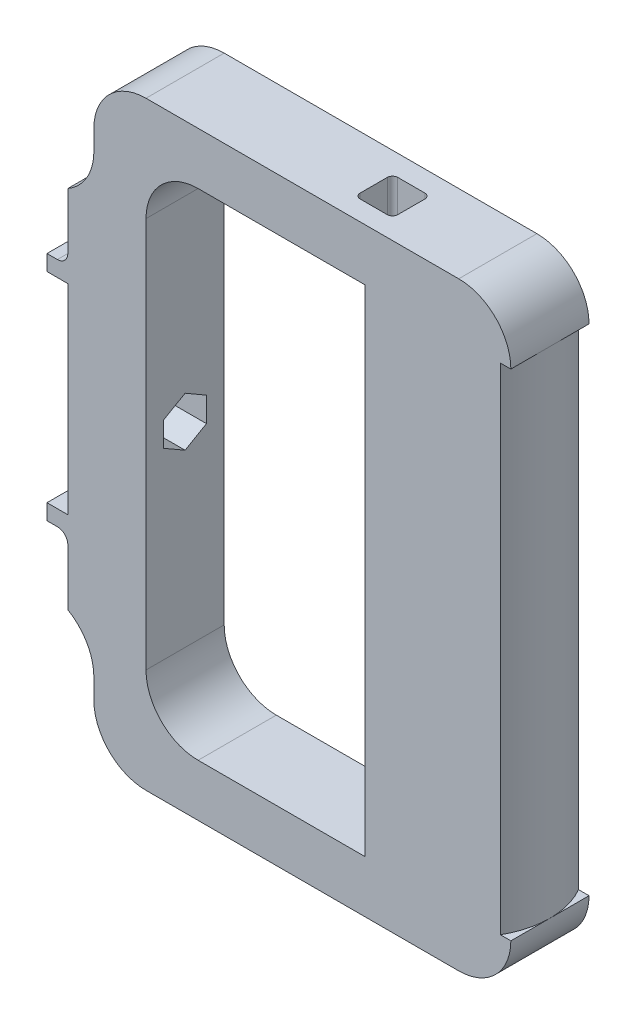
SolidWorks part; units mm, degrees
material "ABS"
ref_plane "Front Plane" through (0, 0, 0) normal (0, 0, 1) x (1, 0, 0)
ref_plane "Top Plane" through (0, 0, 0) normal (0, 1, 0) x (1, 0, 0)
ref_plane "Right Plane" through (0, 0, 0) normal (1, 0, 0) x (0, 0, -1)
sketch "Model" plane through (0, 0, 0) normal (0, 0, 1) x (1, 0, 0)
  line L0 (80, 115) -> (80, 105)
  line L1 (80, 0) -> (80, 10)
  line L8 (-5, 92.5) -> (0, 92.5)
  line L9 (-5, 22.5) -> (0, 22.5)
  line L10 (-5, 92.5) -> (-5, 22.5)
  line L11 (0, 115) -> (80, 115)
  line L12 (0, 0) -> (80, 0)
  line L13 (80, 105) -> (10, 105)
  line L14 (80, 10) -> (10, 10)
  line L16 (10, 105) -> (10, 10)
  line L17 (0, 115) -> (0, 92.5)
  line L19 (0, 0) -> (0, 22.5)
  dimension "D1" = 10
  dimension "D2" = 10
  dimension "D3" = 5
  dimension "D4" = 10
  dimension "D5" = 10
  dimension "D6" = 70
  dimension "D7" = 70
  dimension "D8" = 22.5
  dimension "D9" = 70
  dimension "D10" = 22.5
extrude "Main Body" add sketch "Model" along normal blind 15
sketch "Sketch2" plane through (-5, 0, 0) normal (-1, 0, 0) x (0, 0, 1)
  line L0 (15, 92.5) -> (0, 92.5) construction
  line L2 (7.5, 92.5) -> (7.5, 22.5) construction
  line L3 (15, 22.5) -> (0, 22.5) construction
  circle A0 centre (7.5, 57.5) radius 2.725
  dimension "D3" = 5.45
extrude "M5 Hole" cut sketch "Sketch2" against normal up to next
sketch "Sketch6" plane through (0, 105, 0) normal (0, -1, 0) x (1, 0, 0)
  line L1 (52.0096, 15) -> (77.9904, 15)
  line L2 (52.0096, 0) -> (77.9904, 0)
  line L3 (10, 15) -> (80, 15) construction
  line L4 (10, 0) -> (80, 0) construction
  line L5 (10, 15) -> (10, 0) construction
  line L6 (80, 15) -> (80, 0) construction
  arc A0 (52.0096, 15) -> (52.0096, 0) centre (65, 7.5) ccw
  arc A1 (77.9904, 15) -> (77.9904, 0) centre (65, 7.5) cw
  dimension "D3" = 15
  dimension "D4" = 15
  dimension "D5" = 15
  dimension "D2" = 7.5
extrude "Grip" add sketch "Sketch6" along normal up to next
sketch "Sketch8" plane through (0, 115, 0) normal (0, 1, 0) x (1, 0, 0)
  line L0 (80, -15) -> (80, 0) construction
  line L2 (80, 0) -> (0, 0) construction
  line L3 (46.3, -4) -> (53.5, -4)
  line L4 (46.3, -4) -> (46.3, -11.2)
  line L5 (46.3, -11.2) -> (53.5, -11.2)
  line L6 (53.5, -4) -> (53.5, -11.2)
  line L7 (46.3, -4) -> (53.5, -11.2) construction
  line L8 (46.3, -11.2) -> (53.5, -4) construction
  dimension "D2" = 7.2
  dimension "D3" = 26.5
  dimension "D4" = 4
extrude "Button 1" cut sketch "Sketch8" against normal blind 7
sketch "Sketch9" plane through (0, 108, 0) normal (0, 1, 0) x (1, 0, 0)
  line L4 (46.3, -4) -> (46.3, -11.2) construction
  line L5 (46.3, -11.2) -> (53.5, -11.2) construction
  circle A0 centre (49.7986, -7.7) radius 2
  point P3 (46.3, -7.6)
  dimension "D1" = 4
  dimension "D2" = 3.5
  dimension "D3" = 3.5
extrude "Hole Wires Button 1" cut sketch "Sketch9" against normal blind 3
fillet "Outer Fillet" radius 10 8 edges at (80, 115, 7.5) (80, 0, 7.5) (0, 0, 7.5) (0, 22.5, 7.5) (10, 10, 7.5) (10, 105, 7.5) (0, 92.5, 7.5) (0, 115, 7.5)
sketch "Sketch13" plane through (0, 0, 0) normal (0, 0, -1) x (-1, 0, 0)
  line L0 (-70, 115) -> (-10, 115) construction
  line L2 (-13.7, 112) -> (-6.5, 112)
  line L3 (-13.7, 112) -> (-13.7, 104.8)
  line L4 (-13.7, 104.8) -> (-6.5, 104.8)
  line L5 (-6.5, 112) -> (-6.5, 104.8)
  line L6 (-13.7, 112) -> (-6.5, 104.8) construction
  line L7 (-13.7, 104.8) -> (-6.5, 112) construction
  line L8 (0, 105) -> (0, 101.1603) construction
  point P3 (-10.1, 108.4)
  dimension "D2" = 7.2
  dimension "D3" = 3
  dimension "D4" = 6.5
extrude "Button 2" cut sketch "Sketch13" against normal blind 10
fillet "Buttons Fillet" radius 1 8 edges at (53.5, 111.5, 4) (53.5, 111.5, 11.2) (46.3, 111.5, 4) (46.3, 111.5, 11.2) (6.5, 104.8, 5) (13.7, 104.8, 5) (13.7, 112, 5) (6.5, 112, 5)
ref_plane "Wire Routing Plane" through (10, 0, 0) normal (1, 0, 0) x (0, 0, -1)
sketch "Sketch16" plane through (10, 0, 0) normal (1, 0, 0) x (0, 0, -1)
  line L0 (0, 95) -> (-15, 95) construction
  circle A0 centre (-7.5, 105) radius 2
  point P0 (-7.5, 95)
  dimension "D1" = 10
  dimension "D2" = 4
  dimension "D3" = 7.5
extrude "Wire Routing" cut sketch "Sketch16" against normal mid plane 80
sketch "Sketch17" plane through (10, 0, 0) normal (1, 0, 0) x (0, 0, -1)
  line L1 (-7.5, 62.2343) -> (-11.6, 59.8671)
  line L2 (-11.6, 59.8671) -> (-11.6, 55.1329)
  line L3 (-11.6, 55.1329) -> (-7.5, 52.7657)
  line L4 (-7.5, 52.7657) -> (-3.4, 55.1329)
  line L5 (-3.4, 55.1329) -> (-3.4, 59.8671)
  line L6 (-3.4, 59.8671) -> (-7.5, 62.2343)
  line L14 (0, 20) -> (0, 95) construction
  line L15 (0, 95) -> (-15, 95) construction
  circle A0 centre (-7.5, 57.5) radius 4.1 construction
  dimension "D1" = 8.2
extrude "M5 Nut" cut sketch "Sketch17" against normal blind 6
sketch "Sketch18" plane through (-5, 0, 0) normal (-1, 0, 0) x (0, 0, 1)
  line L0 (0, 92.5) -> (0, 22.5) construction
  line L1 (0, 79.7) -> (15, 79.7)
  line L2 (0, 79.7) -> (0, 76.7)
  line L3 (0, 76.7) -> (15, 76.7)
  line L4 (15, 79.7) -> (15, 76.7)
  line L5 (15, 92.5) -> (15, 22.5) construction
  line L6 (0, 57.5) -> (15, 57.5) construction
  line L7 (0, 38.3) -> (15, 38.3)
  line L8 (0, 38.3) -> (0, 35.3)
  line L9 (0, 35.3) -> (15, 35.3)
  line L10 (15, 38.3) -> (15, 35.3)
  dimension "D1" = 3
  dimension "D3" = 38.4
extrude "Dovetail Male Slot" add sketch "Sketch18" along normal blind 4
fillet "Dovetail Male Slot Fillet" radius 2 2 edges at (-5, 35.3, 7.5)
equation "\"print_free\"= 0.45mm"
equation "\"print_fit\"= 0.2mm"
equation "\"D3@Sketch2\"=5.00mm+\"print_free\""
equation "\"D2@Sketch8\"= 7.00mm+\"print_fit\""
equation "\"D2@Sketch13\"=7.00mm+\"print_fit\""
equation "\"D1@Sketch17\"=8.00mm+\"print_fit\""
equation "\"D3@Sketch18\"=38.00mm+2*\"print_fit\""
